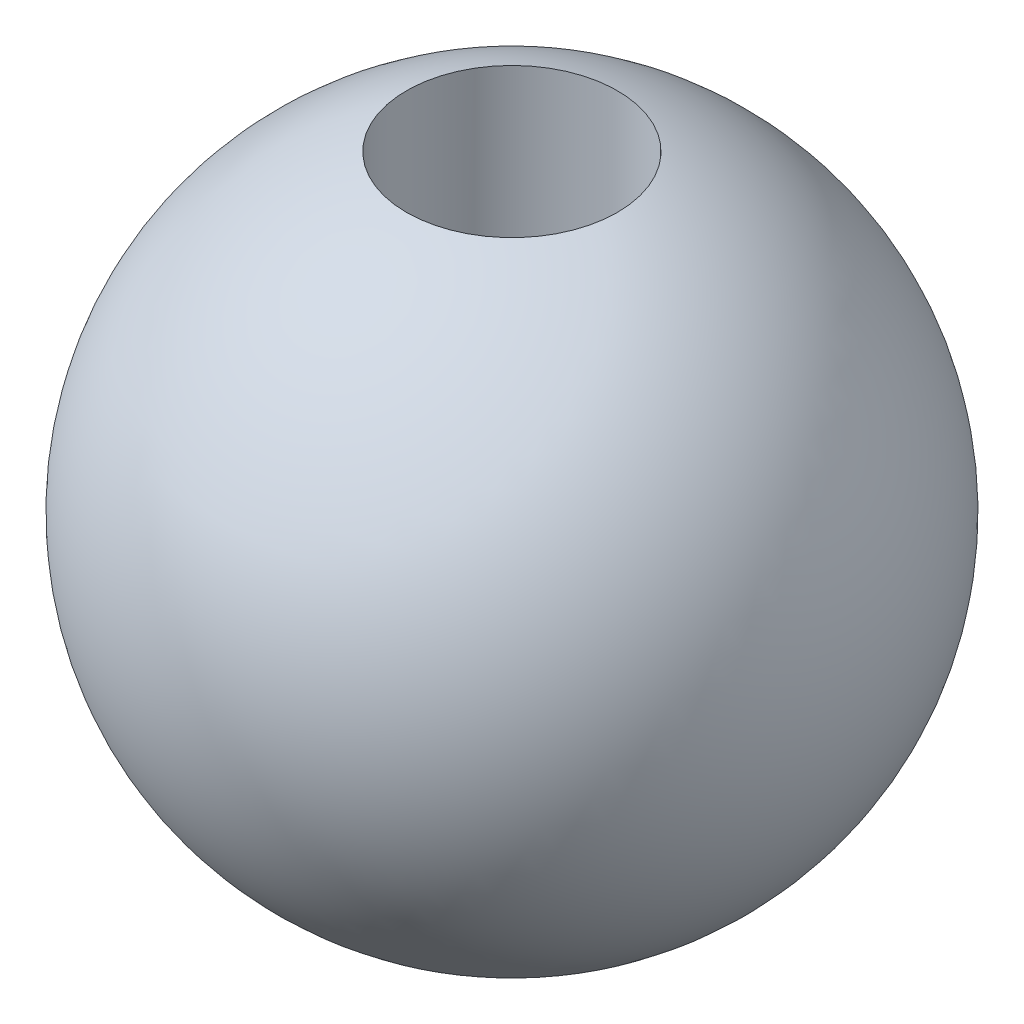
SolidWorks part; units mm, degrees
ref_plane "Vorne" through (0, 0, 0) normal (0, 0, 1) x (1, 0, 0)
ref_plane "Oben" through (0, 0, 0) normal (0, 1, 0) x (1, 0, 0)
ref_plane "Rechts" through (0, 0, 0) normal (1, 0, 0) x (0, 0, -1)
sketch "Skizze1" plane through (0, 0, 0) normal (0, 0, 1) x (1, 0, 0)
  line L0 (0, 12.5) -> (0, -12.5)
  line L1 (0, 27.4263) -> (0, -28.1601) construction
  line L2 (0, -13.027) -> (0, 13.027) construction
  arc A0 (0, 12.5) -> (0, -12.5) centre (0, 0) ccw
  dimension "D1" = 12.5
revolve "Rotation1" add sketch "Skizze1" angle 360 about L1
sketch "Skizze3" plane through (0, 0, 0) normal (0, 1, 0) x (1, 0, 0)
  circle A0 centre (0, 0) radius 4
  dimension "D1" = 8
extrude "Schnitt-Linear austragen1" cut sketch "Skizze3" against normal mid plane 40
sketch "Skizze5" plane through (0, 0, 0) normal (1, 0, 0) x (0, 0, -1)
  line L0 (0, 0) -> (0, 4.8767) construction
  line L1 (-2.15, 0) -> (-2.15, 2)
  line L2 (-2.15, 2) -> (-5, 3.7125)
  line L3 (-5, 3.7125) -> (-5, 0)
  line L4 (-5, 0) -> (-2.15, 0)
  line L5 (13.75, 0) -> (-13.75, 0) construction
  dimension "D1" = 4.3
  dimension "D2" = 59
  dimension "D3" = 10
  dimension "D4" = 2
revolve "Rotation2" add sketch "Skizze5" angle 360 about L0
mirror "Spiegeln1" about plane through (0, 0, 0) normal (0, 1, 0) of "Rotation2"
ref_axis "Achse1" through (13.75, 0, 0) along (-1, 0, 0)
ref_plane "Flexion" through (0, 0, 0) normal (0, 0.9962, -0.0872) x (1, 0, 0)
ref_plane "Extension" through (0, 0, 0) normal (0, 0.9994, 0.0349) x (1, 0, 0)
ref_axis "Achse2" through (0, 0, 14.7952) along (0, 0, -1)
ref_plane "Lateral" through (0, 0, 0) normal (0.0872, 0.9962, 0) x (0.9962, -0.0872, 0)
sketch "Skizze6" plane through (0, 0, 0) normal (0, 1, 0) x (1, 0, 0)
  circle A0 centre (0, 0) radius 5.15
  dimension "D1" = 10.3
extrude "Schnitt-Linear austragen2" cut sketch "Skizze6" against normal through all from offset 2 offset against normal yes
